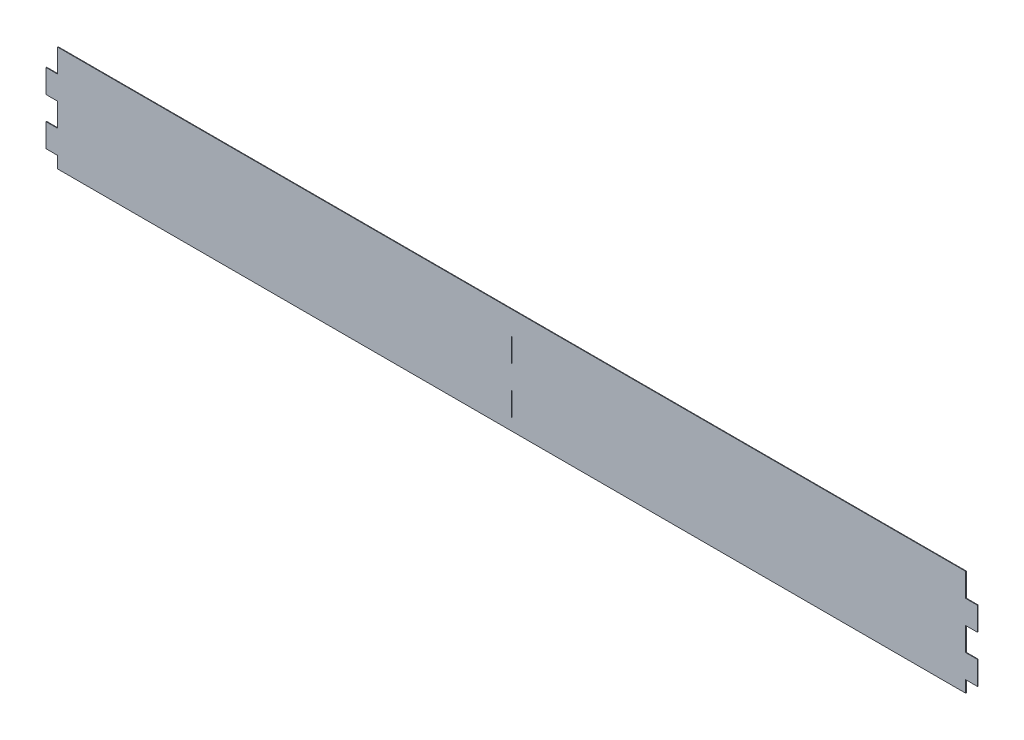
SolidWorks part; units mm, degrees
ref_plane "Front Plane" through (0, 0, 0) normal (0, 0, 1) x (1, 0, 0)
ref_plane "Top Plane" through (0, 0, 0) normal (0, 1, 0) x (1, 0, 0)
ref_plane "Right Plane" through (0, 0, 0) normal (1, 0, 0) x (0, 0, -1)
sketch "Sketch1" plane through (0, 0, 0) normal (0, 0, 1) x (1, 0, 0)
  line L0 (198.5, 45) -> (198.5, 0)
  line L1 (0, 0) -> (193.5, 0)
  line L2 (-198.5, 45) -> (-193.5, 45)
  line L3 (193.5, 45) -> (-193.5, 45)
  line L4 (193.5, 0) -> (198.5, 0)
  line L6 (198.5, 45) -> (193.5, 45)
  line L7 (-198.5, 0) -> (-198.5, 45)
  line L8 (-193.5, 0) -> (-198.5, 0)
  line L9 (0, 0) -> (-193.5, 0)
  point P13 (0, 45)
  dimension "D1" = 5
  dimension "D2" = 387
  dimension "D3" = 5
  dimension "D4" = 45
  dimension "D5" = 45
extrude "Boss-Extrude1" add sketch "Sketch1" along normal mid plane 0.25
sketch "Sketch2" plane through (0, 0, 0.125) normal (0, 0, 1) x (1, 0, 0)
  line L0 (0, 0) -> (0, 75.1617) construction
  line L1 (198.5, 45) -> (-198.5, 45) construction
  line L2 (-0.15, 35) -> (0.15, 35)
  line L3 (-0.15, 35) -> (-0.15, 25)
  line L4 (-0.15, 25) -> (0.15, 25)
  line L5 (0.15, 35) -> (0.15, 25)
  line L6 (-0.15, 35) -> (0.15, 25) construction
  line L7 (-0.15, 25) -> (0.15, 35) construction
  point P3 (0, 30)
  dimension "D1" = 10
  dimension "D2" = 10
  dimension "D3" = 0.3
extrude "Cut-Extrude1" cut sketch "Sketch2" against normal through all
pattern_linear "LPattern1" count 3 spacing 20 along (0, -1, 0) of "Cut-Extrude1"
sketch "Sketch3" plane through (0, 0, 0.125) normal (0, 0, 1) x (1, 0, 0)
  line L1 (-198.5, 45) -> (-193.5, 45)
  line L2 (-198.5, 45) -> (-198.5, 35)
  line L3 (-198.5, 35) -> (-193.5, 35)
  line L4 (-193.5, 45) -> (-193.5, 35)
  dimension "D1" = 5
  dimension "D2" = 10
extrude "Cut-Extrude2" cut sketch "Sketch3" against normal through all
pattern_linear "LPattern2" count 3 spacing 20 along (0, -1, 0) count 2 spacing 392 along (1, 0, 0) of "Cut-Extrude2"
ref_plane "ArmTopPlane" through (0, 45, 0) normal (0, 1, 0) x (1, 0, 0)
ref_axis "Center Axis" through (0, 5, 0.125) along (0, 1, 0)
